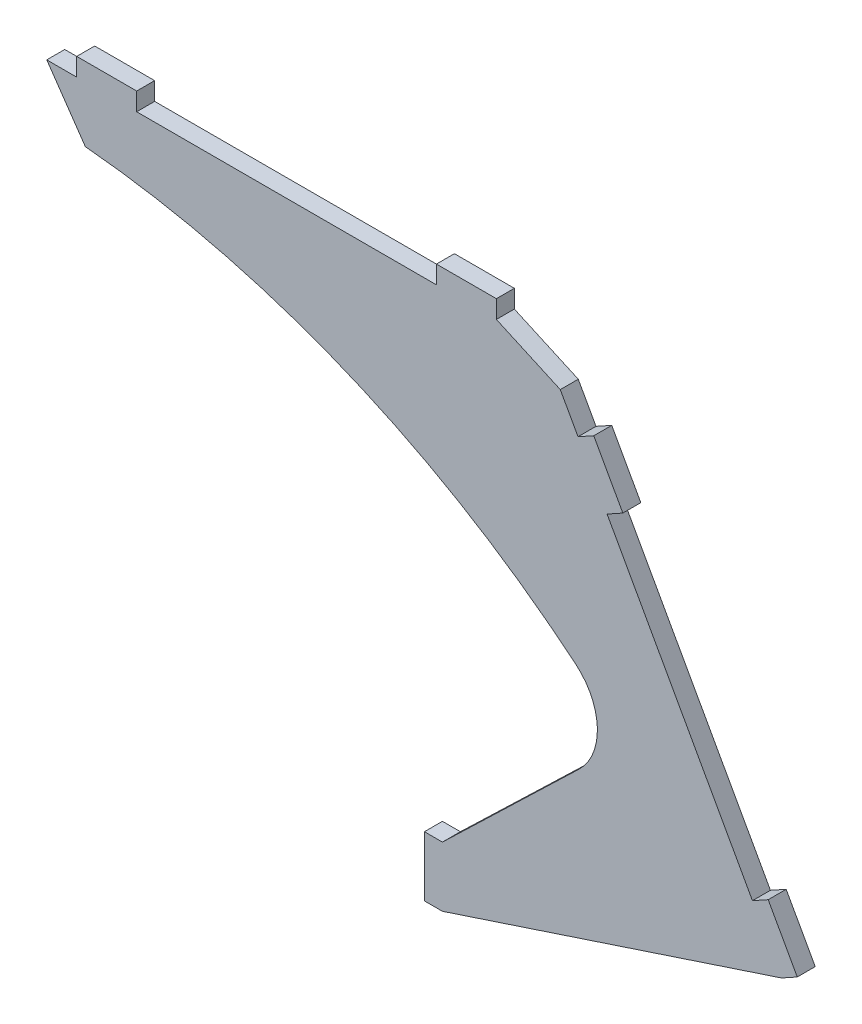
SolidWorks part; units mm, degrees
material "201 Stal nierdzewna odprężona (SS)"
ref_plane "Płaszczyzna przednia" through (0, 0, 0) normal (0, 0, 1) x (1, 0, 0)
ref_plane "Płaszczyzna górna" through (0, 0, 0) normal (0, 1, 0) x (1, 0, 0)
ref_plane "Płaszczyzna prawa" through (0, 0, 0) normal (1, 0, 0) x (0, 0, -1)
sketch "Szkic1" plane through (0, 0, 0) normal (0, 0, 1) x (1, 0, 0)
  line L0 (19.5545, 17.6924) -> (42.339, 39.6144)
  line L1 (19.5545, 17.6924) -> (16.5545, 17.6924)
  line L2 (19.5545, 7.6924) -> (16.5545, 7.6924)
  line L3 (76.1218, 26.3416) -> (19.5545, 7.6924)
  line L4 (76.1218, 26.3416) -> (78.7454, 27.7965)
  line L5 (71.2721, 35.0869) -> (73.8957, 36.5418)
  line L6 (28.5545, 97.6924) -> (39.2174, 92.8905)
  line L7 (-31.4455, 100.6924) -> (-31.4455, 97.6924)
  line L8 (-41.4455, 100.6924) -> (-41.4455, 97.6924)
  line L9 (-46.4455, 97.6924) -> (-40.0031, 88.3723)
  line L10 (-41.4455, 100.6924) -> (-31.4455, 100.6924)
  line L11 (-31.4455, 97.6924) -> (18.5545, 97.6924)
  line L12 (44.7977, 89.0137) -> (49.6473, 80.2684)
  line L13 (47.0237, 78.8135) -> (71.2721, 35.0869)
  line L14 (73.8957, 36.5418) -> (78.7454, 27.7965)
  line L15 (16.5545, 17.6924) -> (16.5545, 7.6924)
  line L16 (-46.4455, 97.6924) -> (-41.4455, 97.6924)
  line L17 (18.5545, 100.6924) -> (18.5545, 97.6924)
  line L18 (28.5545, 100.6924) -> (28.5545, 97.6924)
  line L19 (18.5545, 100.6924) -> (28.5545, 100.6924)
  line L20 (47.0237, 78.8135) -> (49.6473, 80.2684)
  line L21 (42.1741, 87.5588) -> (44.7977, 89.0137)
  line L22 (39.2174, 92.8905) -> (42.1741, 87.5588)
  arc A0 (41.7905, 54.517) -> (-40.0031, 88.3723) centre (-53.8143, -60.7282) ccw
  arc A1 (42.339, 39.6144) -> (41.7905, 54.517) centre (35.4057, 46.8206) ccw
extrude "Dodanie-wyciągnięcie1" add sketch "Szkic1" along normal blind 3 contours A0 L9 L16 L8 L10 L7 L11 L17 L19 L18 L6 L22 L21 L12 L20 L13 L5 L14 L4 L3 L2 L15 L1 L0 A1
